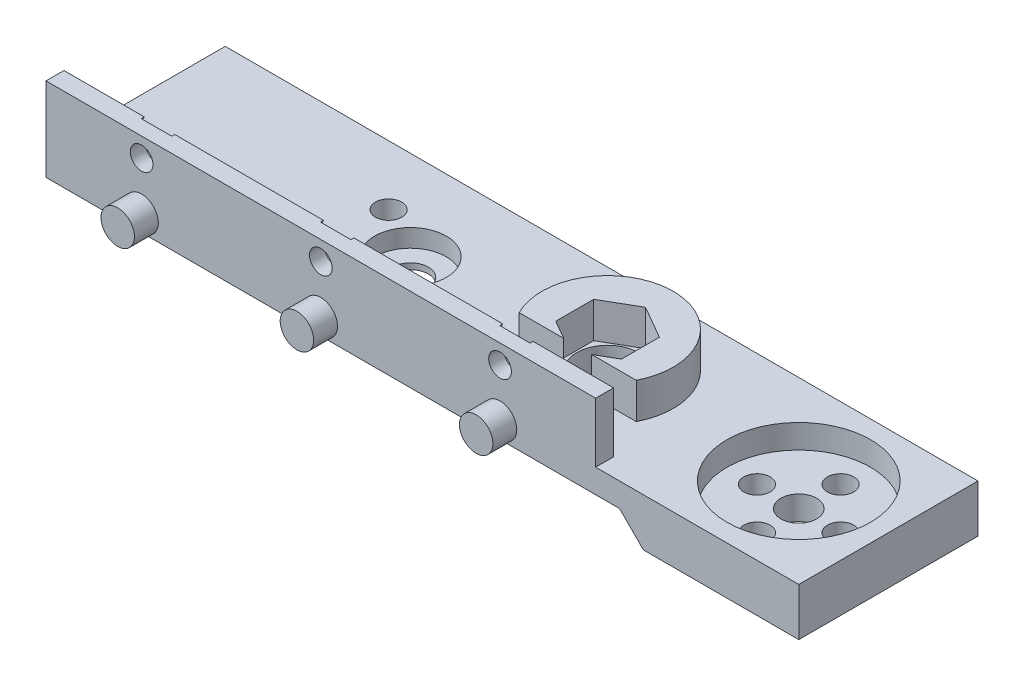
SolidWorks part; units mm, degrees
ref_plane "前视基准面" through (0, 0, 0) normal (0, 0, 1) x (1, 0, 0)
ref_plane "上视基准面" through (0, 0, 0) normal (0, 1, 0) x (1, 0, 0)
ref_plane "右视基准面" through (0, 0, 0) normal (1, 0, 0) x (0, 0, -1)
other "Configuration Table"
sketch "草图1" plane through (0, 0, 0) normal (0, 1, 0) x (1, 0, 0)
  line L0 (-31.5, 7.5) -> (31.5, 7.5)
  line L1 (31.5, 7.5) -> (31.5, -7.5)
  line L2 (31.5, -7.5) -> (-31.5, -7.5)
  line L3 (-31.5, -7.5) -> (-31.5, 7.5)
  line L4 (-31.5, 0) -> (31.5, 0) construction
  line L5 (-12.8301, -2.5) -> (-4.1699, 2.5) construction
  line L6 (-13.3083, -5.95) -> (-3.6917, -5.95) construction
  line L7 (-13.3083, 5.95) -> (-3.6917, 5.95) construction
  line L8 (-8.5, 7.5) -> (-8.5, -7.5) construction
  line L9 (8, 0) -> (8, 4.5778) construction
  line L11 (31.5, 7.5) -> (16.5, 7.5)
  line L12 (31.5, 7.5) -> (31.5, -7.5)
  line L13 (31.5, -7.5) -> (16.5, -7.5)
  line L14 (16.5, 7.5) -> (16.5, -7.5)
  circle A0 centre (-8.5, 0) radius 1.5
  circle A1 centre (-4.1699, 2.5) radius 1.1
  circle A3 centre (-12.8301, -2.5) radius 1.1
  arc A4 (-13.3083, 5.95) -> (-13.3083, -5.95) centre (-8.5, 0) ccw construction
  circle A5 centre (8, 0) radius 2.6
  arc A6 (-3.6917, -5.95) -> (-3.6917, 5.95) centre (-8.5, 0) ccw construction
  circle A7 centre (24, 0) radius 1.5
  circle A8 centre (24, 0) radius 3.5 construction
  circle A9 centre (27.5, 0) radius 1.1
  circle A10 centre (24, -3.5) radius 1.1
  circle A11 centre (20.5, 0) radius 1.1
  circle A12 centre (24, 3.5) radius 1.1
  circle A13 centre (-12.8301, 2.5) radius 1.1
  circle A14 centre (-4.1699, -2.5) radius 1.1
  circle A21 centre (24, 0) radius 6
  point P5 (0, 7.5)
  point P7 (-31.5, 0)
  dimension "D3" = 3
  dimension "D6" = 2.2
  dimension "D9" = 15.3
  dimension "D12" = 5.2
  dimension "D14" = 3
  dimension "D15" = 7
  dimension "D16" = 2.2
  dimension "D22" = 12
  dimension "D1" = 63
  dimension "D2" = 15
  dimension "D4" = 23
  dimension "D7" = 30
  dimension "D8" = 10
  dimension "D10" = 11.9
  dimension "D11" = 16.5
  dimension "D13" = 16
  dimension "D21" = 15
  dimension "D5" = 2
  dimension "D17" = 4
extrude "凸台-拉伸1" add sketch "草图1" along normal blind 2 contours A3 | L14 L0 L3 L2 A13 A3 A1 A0 A14 | L0 L14 L2 L1 A21 | A21 A7 A9 A10 A11 A12 | A5 | A1 region at (-7.5, 0, -6.9971) region at (24, 0, -7.2879) region at (-4.1699, 0, -2.5) region at (-12.8301, 0, 2.5) region at (18.1697, 0, 0)
sketch "草图2" plane through (0, 0, 7.5) normal (0, 0, 1) x (1, 0, 0)
  line L0 (-31, 1.4) -> (31, 1.4) construction
  line L1 (-31.5, 2) -> (-31.5, 0) construction
  line L3 (31.5, 0) -> (-31.5, 0) construction
  circle A0 centre (-23.5, 1.4) radius 1.4
  circle A1 centre (-8.5, 1.4) radius 1.4
  circle A2 centre (6.5, 1.4) radius 1.4
  circle A3 centre (-23.5, 5.4) radius 0.95
  circle A4 centre (-8.5, 5.4) radius 0.95
  circle A5 centre (6.5, 5.4) radius 0.95
  line M10 (31.5, 2) -> (-31.5, 2)
  dimension "D1" = 2.8
  dimension "D2" = 2.8
  dimension "D3" = 2.8
  dimension "D8" = 1.9
  dimension "D4" = 15
  dimension "D5" = 15
  dimension "D6" = 8
  dimension "D7" = 1.4
  dimension "D9" = 4
  dimension "D10" = 3
extrude "凸台-拉伸2" add sketch "草图2" along normal blind 2 contours L0 A0 | A0 L0 M10 | A0 M10 | L0 A1 | A1 L0 M10 | A1 M10 | L0 A2 | A2 L0 M10 | A2 M10 region at (-23.5, 1.6951, 7.5) region at (-23.5, 0.8058, 7.5) region at (-23.5, 2.3294, 7.5) region at (-8.5, 1.6951, 7.5) region at (-8.5, 0.8058, 7.5) region at (-8.5, 2.3294, 7.5) region at (6.5, 1.6951, 7.5) region at (6.5, 0.8058, 7.5) region at (6.5, 2.3294, 7.5)
sketch "草图3" plane through (0, 2, 0) normal (0, 1, 0) x (1, 0, 0)
  text T0 "R" font "Microsoft YaHei UI" height 3.5
sketch "草图4" plane through (0, 2, 0) normal (0, 1, 0) x (1, 0, 0)
  circle A0 centre (-8.5, 0) radius 3
  dimension "D1" = 6
extrude "切除-拉伸1" cut sketch "草图4" against normal blind 1.5
sketch "草图5" plane through (0, 2, 0) normal (0, 1, 0) x (1, 0, 0)
  line L1 (-31.5, -7.5) -> (14.5, -7.5)
  line L2 (-31.5, -7.5) -> (-31.5, -6)
  line L3 (-31.5, -6) -> (14.5, -6)
  line L4 (14.5, -7.5) -> (14.5, -6)
  dimension "D1" = 1.5
  dimension "D2" = 46
extrude "凸台-拉伸3" add sketch "草图5" along normal blind 5
extrude "切除-拉伸2" cut sketch "草图2<3>" against normal blind 6 contours A3 | A4 | A5 region at (-23.5, 5.4, 7.5) region at (-8.5, 5.4, 7.5) region at (6.5, 5.4, 7.5)
sketch "草图2<3>" plane through (0, 0, 7.5) normal (0, 0, 1) x (1, 0, 0) same geometry as "草图2"
sketch "草图7" plane through (0, 0, 6) normal (0, 0, -1) x (-1, 0, 0)
  line L0 (-7.597, 3.5) -> (-5.403, 3.5)
  line L1 (-5.403, 3.5) -> (-4.3061, 5.4)
  line L2 (-4.3061, 5.4) -> (-5.403, 7.3)
  line L3 (-5.403, 7.3) -> (-7.597, 7.3)
  line L4 (-7.597, 7.3) -> (-8.6939, 5.4)
  line L5 (-8.6939, 5.4) -> (-7.597, 3.5)
  line L6 (-7.597, 7.3) -> (-5.403, 3.5) construction
  line L7 (-5.403, 7.3) -> (-7.597, 3.5) construction
  line L8 (6.3061, 5.4) -> (7.403, 3.5)
  line L9 (7.403, 3.5) -> (9.597, 3.5)
  line L10 (9.597, 3.5) -> (10.6939, 5.4)
  line L11 (10.6939, 5.4) -> (9.597, 7.3)
  line L12 (9.597, 7.3) -> (7.403, 7.3)
  line L13 (7.403, 7.3) -> (6.3061, 5.4)
  line L14 (21.3061, 5.4) -> (22.403, 3.5)
  line L15 (22.403, 3.5) -> (24.597, 3.5)
  line L16 (24.597, 3.5) -> (25.6939, 5.4)
  line L17 (25.6939, 5.4) -> (24.597, 7.3)
  line L18 (24.597, 7.3) -> (22.403, 7.3)
  line L19 (22.403, 7.3) -> (21.3061, 5.4)
  line L20 (7.403, 7.3) -> (9.597, 3.5) construction
  line L21 (9.597, 7.3) -> (7.403, 3.5) construction
  circle A0 centre (-6.5, 5.4) radius 0.95
  circle A1 centre (-6.5, 5.4) radius 0.95 construction
  circle A2 centre (8.5, 5.4) radius 0.95
  circle A3 centre (8.5, 5.4) radius 0.95 construction
  point P11 (-6.5, 5.4)
  point P29 (8.5, 5.4)
  dimension "D1" = 3.8
  dimension "D2" = 3.8
  dimension "D3" = 3.8
  dimension "D4" = 120
  dimension "D5" = 120
  dimension "D6" = 120
  dimension "D7" = 3
extrude "切除-拉伸3" cut sketch "草图7" against normal blind 0.25
extrude "凸台-拉伸4" add sketch "草图1<3>" along normal blind 2 contours L0 L14 L2 L1 A21 | A21 A7 A9 A10 A11 A12 region at (24, 0, -7.2879) region at (18.1697, 0, 0)
sketch "草图1<3>" plane through (0, 0, 0) normal (0, 1, 0) x (1, 0, 0) same geometry as "草图1"
extrude "凸台-拉伸5" add sketch "草图1<4>" against normal blind 2 contours L0 L14 L2 L1 A21 | A21 A7 A9 A10 A11 A12 region at (24, 0, -7.2879) region at (18.1697, 0, 0)
sketch "草图1<4>" plane through (0, 0, 0) normal (0, 1, 0) x (1, 0, 0) same geometry as "草图1"
extrude "切除-拉伸4" cut sketch "草图1<5>" along normal up to surface (2 mm away) contours A21 up to face at (4.8333, 2, 2)
sketch "草图1<5>" plane through (0, 0, 0) normal (0, 1, 0) x (1, 0, 0) same geometry as "草图1"
sketch "草图8" plane through (0, 0, -7.5) normal (0, 0, -1) x (-1, 0, 0)
  line L0 (-16.5, 0) -> (-18.5, -2)
  line L1 (-16.5, -2) -> (-31.5, -2) construction
  line L2 (-18.5, -2) -> (-16.5, -2)
  line L3 (-16.5, -2) -> (-16.5, 0)
  dimension "D1" = 45
extrude "切除-拉伸5" cut sketch "草图8" against normal up to surface (15 mm away) up to face at (1.0857, 1.3, 7.5)
sketch "草图9" plane through (0, 2, 0) normal (0, 1, 0) x (1, 0, 0)
  circle A0 centre (8, 0) radius 2.6
  circle A1 centre (8, 0) radius 5.5
  circle A2 centre (8, 0) radius 2.6 construction
  dimension "D1" = 11
extrude "凸台-拉伸6" add sketch "草图9" along normal blind 3
sketch "草图10" plane through (0, 5, 0) normal (0, 1, 0) x (1, 0, 0)
  line L0 (8, 0) -> (1.5791, 0) construction
  line L1 (8, 0) -> (8, 6.1954) construction
  line L2 (8, 3.1754) -> (5.25, 1.5877)
  line L3 (5.25, 1.5877) -> (5.25, -1.5877)
  line L4 (8, 3.1754) -> (10.75, 1.5877)
  line L5 (10.75, 1.5877) -> (10.75, -1.5877)
  line L6 (8, -3.1754) -> (10.75, -1.5877)
  line L7 (8, -3.1754) -> (5.25, -1.5877)
  line L8 (3.101, -2.5) -> (12.899, -2.5)
  line L9 (14.5, -6) -> (7.7702, -6) construction
  circle A0 centre (8, 0) radius 5.5 construction
  circle A1 centre (8, 0) radius 5.5 construction
  arc A2 (12.899, -2.5) -> (3.101, -2.5) centre (8, 0) cw
  point P11 (10.75, 0)
  point P13 (5.25, 0)
  circle M8 centre (8, 0) radius 5.5
  circle M9 centre (8, 0) radius 2.6
  dimension "D1" = 120
  dimension "D2" = 5.5
  dimension "D3" = 5.5
  dimension "D4" = 3.5
extrude "切除-拉伸6" cut sketch "草图10" against normal up to surface (3 mm away) contours L8 L6 L7 M8 | L8 L7 L6 M9 region at (8, 5, 2.7506) region at (8, 5, 3.7728) up to face at (-8.5, 2, 3)
extrude "切除-拉伸7" cut sketch "草图10<3>" against normal blind 3.5 contours L7 L8 L6 L5 L4 L2 L3 M9 region at (9.3355, 5, -2.3131)
sketch "草图10<3>" plane through (0, 5, 0) normal (0, 1, 0) x (1, 0, 0) same geometry as "草图10"
extrude "凸台-拉伸7" add sketch "草图9<2>" against normal blind 4
sketch "草图9<2>" plane through (0, 2, 0) normal (0, 1, 0) x (1, 0, 0) same geometry as "草图9"
